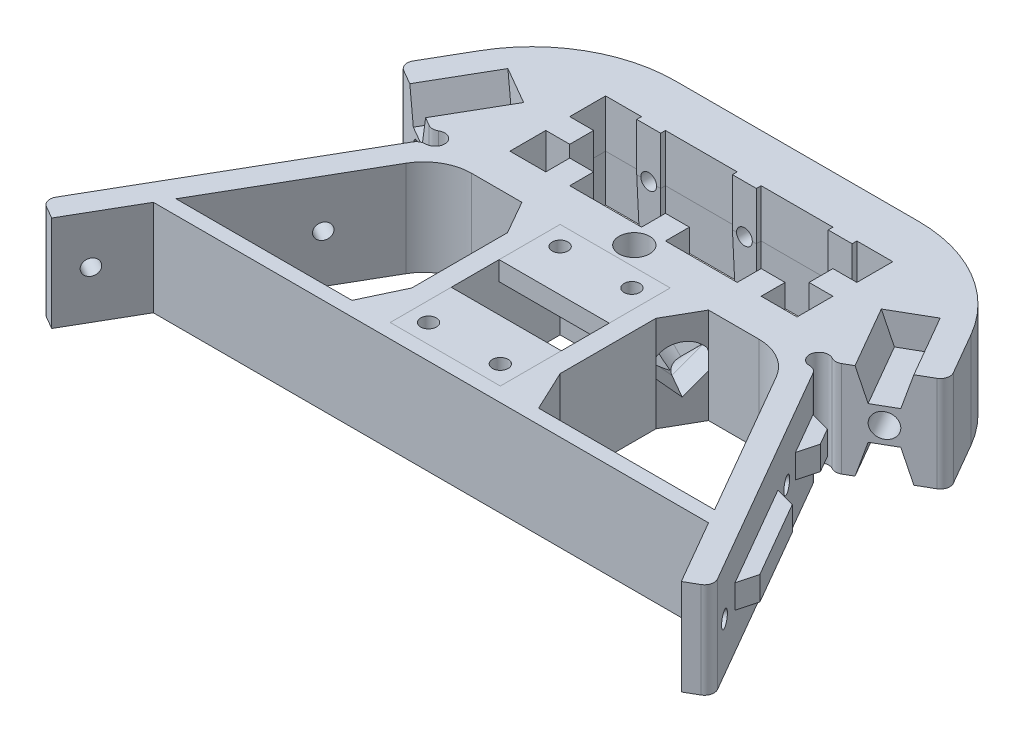
SolidWorks part; units mm, degrees
ref_plane "Front Plane" through (0, 0, 0) normal (0, 0, 1) x (1, 0, 0)
ref_plane "Top Plane" through (0, 0, 0) normal (0, 1, 0) x (1, 0, 0)
ref_plane "Right Plane" through (0, 0, 0) normal (1, 0, 0) x (0, 0, -1)
sketch "Sketch1" plane through (0, 0, 0) normal (0, 1, 0) x (1, 0, 0)
  line L0 (-30, -18) -> (30, -18)
  line L1 (-30, 10) -> (-22.5, 10)
  line L2 (-46.46, 5.4904) -> (-53.96, -7.5) construction
  line L3 (-30, -10) -> (-22.5, -10)
  line L4 (30, 10) -> (30, 2.5)
  line L5 (0, 0) -> (0, -75.5561) construction
  line L6 (38.6603, -23) -> (65.7735, -69.9615)
  line L7 (65.7735, -69.9615) -> (68.3716, -68.4615)
  line L8 (69.1036, -65.7295) -> (41.8357, -18.5)
  line L9 (43.1036, -13.7679) -> (55.6921, -6.5)
  line L10 (56.4241, -3.7679) -> (51.362, 5)
  line L11 (25.3812, 20) -> (-25.3812, 20)
  line L12 (43.5677, -13.5) -> (36.0677, -0.5096) construction
  line L13 (36.0677, -0.5096) -> (46.46, 5.4904) construction
  line L14 (46.46, 5.4904) -> (53.96, -7.5) construction
  line L15 (-36.0677, -0.5096) -> (-46.46, 5.4904) construction
  line L16 (-43.5677, -13.5) -> (-36.0677, -0.5096) construction
  line L17 (-56.4241, -3.7679) -> (-51.362, 5)
  line L18 (-43.1036, -13.7679) -> (-55.6921, -6.5)
  line L19 (-69.1036, -65.7295) -> (-41.8357, -18.5)
  line L20 (-65.7735, -69.9615) -> (-68.3716, -68.4615)
  line L21 (-38.6603, -23) -> (-65.7735, -69.9615)
  line L22 (-30, 10) -> (-30, 2.5)
  line L23 (30, 2.5) -> (25, 2.5)
  line L24 (25, 2.5) -> (25, -2.5)
  line L25 (25, -2.5) -> (30, -2.5)
  line L26 (30, -2.5) -> (30, -10)
  line L27 (22.5, -10) -> (22.5, -5)
  line L28 (22.5, -5) -> (17.5, -5)
  line L29 (17.5, -5) -> (17.5, -10)
  line L30 (22.5, -10) -> (30, -10)
  line L31 (17.5, 10) -> (17.5, 9)
  line L32 (17.5, 9) -> (22.5, 9)
  line L33 (22.5, 9) -> (22.5, 10)
  line L34 (22.5, 10) -> (30, 10)
  line L35 (2.5, -10) -> (2.5, -5)
  line L36 (2.5, -5) -> (-2.5, -5)
  line L37 (-2.5, -5) -> (-2.5, -10)
  line L38 (-2.5, 10) -> (-2.5, 9)
  line L39 (-2.5, 9) -> (2.5, 9)
  line L40 (2.5, 9) -> (2.5, 10)
  line L41 (-17.5, -10) -> (-17.5, -5)
  line L42 (-17.5, -5) -> (-22.5, -5)
  line L43 (-22.5, -5) -> (-22.5, -10)
  line L44 (-22.5, 10) -> (-22.5, 9)
  line L45 (-22.5, 9) -> (-17.5, 9)
  line L46 (-17.5, 9) -> (-17.5, 10)
  line L47 (-17.5, 10) -> (-2.5, 10)
  line L48 (-17.5, -10) -> (-2.5, -10)
  line L49 (2.5, -10) -> (17.5, -10)
  line L50 (2.5, 10) -> (17.5, 10)
  line L51 (-25, -2.5) -> (-30, -2.5)
  line L52 (-25, 2.5) -> (-25, -2.5)
  line L53 (-30, 2.5) -> (-25, 2.5)
  line L54 (-30, -2.5) -> (-30, -10)
  circle A0 centre (0, 0) radius 31.6228 construction
  arc A1 (30, -18) -> (38.6603, -23) centre (30, -28) cw
  arc A2 (51.362, 5) -> (25.3812, 20) centre (25.3812, -10) ccw
  arc A3 (41.1036, -13.7679) -> (40.1036, -17.5) centre (40.1036, -15.5) ccw
  arc A4 (68.3716, -68.4615) -> (69.1036, -65.7295) centre (67.3716, -66.7295) ccw
  arc A5 (55.6921, -6.5) -> (56.4241, -3.7679) centre (54.6921, -4.7679) ccw
  arc A6 (40.1036, -17.5) -> (41.8357, -18.5) centre (40.1036, -19.5) cw
  arc A7 (41.1036, -13.7679) -> (43.1036, -13.7679) centre (42.1036, -12.0359) ccw
  arc A8 (-41.1036, -13.7679) -> (-43.1036, -13.7679) centre (-42.1036, -12.0359) cw
  arc A9 (-40.1036, -17.5) -> (-41.8357, -18.5) centre (-40.1036, -19.5) ccw
  arc A10 (-55.6921, -6.5) -> (-56.4241, -3.7679) centre (-54.6921, -4.7679) cw
  arc A11 (-68.3716, -68.4615) -> (-69.1036, -65.7295) centre (-67.3716, -66.7295) cw
  arc A12 (-41.1036, -13.7679) -> (-40.1036, -17.5) centre (-40.1036, -15.5) cw
  arc A13 (-51.362, 5) -> (-25.3812, 20) centre (-25.3812, -10) cw
  arc A14 (-30, -18) -> (-38.6603, -23) centre (-30, -28) ccw
  point P7 (-57.4241, -5.5)
  point P9 (0, -18)
  point P22 (35.7735, -18)
  point P27 (0, 10)
  point P30 (70.1036, -67.4615)
  point P33 (57.4241, -5.5)
  point P61 (0, 20)
  point P65 (-70.1036, -67.4615)
  point P66 (-35.7735, -18)
  dimension "D12" = 10
  dimension "D14" = 30
  dimension "D16" = 2
  dimension "D17" = 2
  dimension "D2" = 30
  dimension "D3" = 5
  dimension "D4" = 8
  dimension "D5" = 60
  dimension "D6" = 20
  dimension "D7" = 30
  dimension "D8" = 10
  dimension "D9" = 4
  dimension "D10" = 12
  dimension "D11" = 15
  dimension "D13" = 20
  dimension "D18" = 5
  dimension "D19" = 2.5
  dimension "D20" = 5
  dimension "D21" = 5
  dimension "D22" = 5
  dimension "D23" = 7.5
  dimension "D24" = 1
  dimension "D26" = 20
  dimension "D25" = 3
extrude "Boss-Extrude1" add sketch "Sketch1" along normal blind 20
sketch "Sketch2" plane through (16.7376, 0, 28.9904) normal (0.5, 0, 0.866) x (0.866, 0, -0.5)
  line L0 (30.4449, 0) -> (44.9808, 0) construction
  line L1 (26.9808, 20) -> (26.9808, 0) construction
  circle A0 centre (36.9808, 10) radius 5
  dimension "D1" = 10
  dimension "D2" = 10
  dimension "D3" = 10
extrude "Cut-Extrude1" cut sketch "Sketch2" against normal through all
sketch "Sketch3" plane through (16.7376, 0, 28.9904) normal (0.5, 0, 0.866) x (0.866, 0, -0.5)
  circle A0 centre (36.9808, 10) radius 5
  circle A1 centre (36.9808, 10) radius 5 construction
  circle A2 centre (36.9808, 10) radius 2.5
  dimension "D1" = 5
extrude "Boss-Extrude2" add sketch "Sketch3" against normal blind 16
sketch "Sketch4" plane through (16.7376, 0, 28.9904) normal (0.5, 0, 0.866) x (0.866, 0, -0.5)
  line L0 (36.9808, 10) -> (44.9808, 10) construction
  line L1 (44.9808, 20) -> (44.9808, 0) construction
  line L2 (32.4808, 20) -> (34.4808, 13.5)
  line L3 (30.4449, 20) -> (44.9808, 20) construction
  line L4 (34.4808, 13.5) -> (39.4808, 13.5)
  line L5 (39.4808, 13.5) -> (41.4808, 20)
  line L6 (41.4808, 20) -> (32.4808, 20)
  line L7 (36.9808, 13.5) -> (36.9808, 20) construction
  line L8 (41.4808, 0) -> (32.4808, 0)
  line L9 (39.4808, 6.5) -> (41.4808, 0)
  line L10 (34.4808, 6.5) -> (39.4808, 6.5)
  line L11 (32.4808, 0) -> (34.4808, 6.5)
  dimension "D1" = 9
  dimension "D2" = 5
  dimension "D3" = 6.5
extrude "Cut-Extrude2" cut sketch "Sketch4" against normal blind 15
sketch "Sketch7" plane through (0, 0, -20) normal (0, 0, -1) x (-1, 0, 0)
  line L0 (-20, 10) -> (20, 10) construction
  circle A0 centre (-20, 10) radius 1.65
  circle A1 centre (0, 10) radius 1.65
  circle A2 centre (20, 10) radius 1.65
  dimension "D1" = 3.3
  dimension "D3" = 40
  dimension "D4" = 10
  dimension "D2" = 3
extrude "Cut-Extrude4" cut sketch "Sketch7" against normal up to next
sketch "Sketch8" plane through (0, 0, -20) normal (0, 0, -1) x (-1, 0, 0)
  circle A0 centre (-20, 10) radius 6
  circle A1 centre (-20, 10) radius 1.65 construction
  circle A2 centre (0, 10) radius 6
  circle A3 centre (20, 10) radius 6
  circle A4 centre (20, 10) radius 1.65 construction
  dimension "D1" = 12
  dimension "D2" = 3
extrude "Cut-Extrude5" cut sketch "Sketch8" against normal offset from surface (4 mm away) 7 up to face at (1.65, 10, -9)
sketch "Sketch9" plane through (0, 0, 0) normal (0, 1, 0) x (1, 0, 0)
  line L0 (-11.5, -40) -> (11.5, -40) construction
  line L1 (2.5, -10) -> (17.5, -10) construction
  line L2 (-11.5, -30) -> (11.5, -30) construction
  line L3 (-11.5, -30) -> (-11.5, -40)
  line L4 (11.5, -30) -> (11.5, -40)
  line L5 (0, -30) -> (0, 0) construction
  line L6 (-19.5, -18) -> (-15.5, -25)
  line L7 (-30, -18) -> (30, -18) construction
  line L8 (-15.5, -25) -> (-15.5, -45)
  line L9 (-15.5, -45) -> (-19.5, -53.5)
  line L10 (-56.2694, -53.5) -> (-19.5, -53.5)
  line L11 (19.5, -53.5) -> (15.5, -45)
  line L12 (15.5, -45) -> (15.5, -25)
  line L13 (15.5, -25) -> (19.5, -18)
  line L14 (-19.5, -18) -> (-11.5, -18)
  line L15 (-11.5, -35) -> (11.5, -35) construction
  line L16 (11.5, -30) -> (11.5, -18)
  line L17 (-11.5, -30) -> (-11.5, -18)
  line L18 (11.5, -18) -> (19.5, -18)
  line L19 (-11.5, -40) -> (-11.5, -53.5)
  line L20 (-11.5, -53.5) -> (11.5, -53.5)
  line L21 (11.5, -53.5) -> (11.5, -40)
  line L30 (-65.7735, -69.9615) -> (-38.6603, -23) construction
  line L31 (38.6603, -23) -> (65.7735, -69.9615) construction
  line L32 (19.5, -53.5) -> (56.2694, -53.5)
  line L33 (-58.0015, -56.5) -> (58.0015, -56.5)
  line L34 (58.0015, -56.5) -> (56.2694, -53.5)
  line L35 (-58.0015, -56.5) -> (-56.2694, -53.5)
  circle A0 centre (0, -20.5) radius 1.65 construction
  circle A1 centre (0, -49.5) radius 1.65 construction
  dimension "D6" = 3.3
  dimension "D11" = 2.5
  dimension "D1" = 30
  dimension "D2" = 10
  dimension "D3" = 23
  dimension "D4" = 4
  dimension "D5" = 4
  dimension "D7" = 7
  dimension "D8" = 8.5
  dimension "D9" = 7
  dimension "D10" = 20
  dimension "D14" = 4
  dimension "D15" = 4
  dimension "D16" = 4
  dimension "D17" = 3
extrude "Boss-Extrude3" add sketch "Sketch9" along normal up to surface (20 mm away) up to face at (6.0019, 20, 19.8008)
sketch "Sketch11" plane through (23.366, 0, -13.4904) normal (0.866, 0, -0.5) x (-0.5, 0, -0.866)
  line L1 (-81.4752, 12.5) -> (-56.9393, 12.5)
  line L2 (-81.4752, 12.5) -> (-81.4752, 7.5)
  line L3 (-81.4752, 7.5) -> (-56.9393, 7.5)
  line L4 (-36.9393, 12.5) -> (-36.9393, 7.5)
  line L5 (-36.9393, 20) -> (-36.9393, 0) construction
  line L6 (-91.4752, 0) -> (-36.9393, 0) construction
  line L7 (-46.9393, 12.5) -> (-46.9393, 7.5)
  line L8 (-56.9393, 12.5) -> (-56.9393, 7.5)
  line L9 (-46.9393, 12.5) -> (-36.9393, 12.5)
  line L10 (-46.9393, 7.5) -> (-36.9393, 7.5)
  line L11 (-91.4752, 20) -> (-91.4752, 0) construction
  dimension "D1" = 5
  dimension "D2" = 7.5
  dimension "D3" = 10
  dimension "D4" = 10
  dimension "D5" = 10
extrude "Boss-Extrude5" add sketch "Sketch11" along normal blind 3
chamfer "Chamfer1" distance 3 angle 45 4 edges at (44.4338, 10, 17) (49.4338, 10, 25.6603) (54.4338, 10, 34.3205) (66.7017, 10, 55.5692)
sketch "Sketch13" plane through (23.366, 0, -13.4904) normal (0.866, 0, -0.5) x (-0.5, 0, -0.866)
  line L0 (-56.9393, 10) -> (-46.9393, 10) construction
  line L1 (-56.9393, 7.5) -> (-56.9393, 12.5) construction
  line L2 (-46.9393, 12.5) -> (-46.9393, 7.5) construction
  line L3 (-81.4752, 10) -> (-93.4752, 10) construction
  line L4 (-81.4752, 12.5) -> (-81.4752, 7.5) construction
  line L5 (-93.4752, 20) -> (-93.4752, 0) construction
  circle A0 centre (-51.9393, 10) radius 1.65
  circle A1 centre (-87.4752, 10) radius 1.65
  dimension "D1" = 3.3
  dimension "D2" = 3.3
extrude "Cut-Extrude6" cut sketch "Sketch13" against normal up to next
mirror "Mirror2" about plane through (0, 0, 0) normal (1, 0, 0) of "Cut-Extrude6", "Chamfer1", "Boss-Extrude5", "Cut-Extrude2", "Boss-Extrude2", "Cut-Extrude1"
ref_plane "Plane2" through (0, 10, 0) normal (0, 1, 0) x (1, 0, 0)
sketch "Sketch15" plane through (0, 10, 0) normal (0, 1, 0) x (1, 0, 0)
  line L0 (-10, -10) -> (-10, -14.3127)
  line L1 (-17.5, -10) -> (-2.5, -10) construction
  line L2 (-12.5193, -18.6539) -> (-17.5, -21.5)
  line L3 (-19.5, -18) -> (-15.5, -25) construction
  arc A0 (-10, -14.3127) -> (-12.5193, -18.6539) centre (-15, -14.3127) cw
  dimension "D1" = 5
sketch "Sketch16" plane through (0, 0, 10) normal (0, 0, -1) x (-1, 0, 0)
  line L0 (5, 10) -> (10, 5)
  line L1 (10, 5) -> (15, 10)
  arc A0 (15, 10) -> (5, 10) centre (10, 10) ccw
  dimension "D1" = 10
sketch "Sketch17" plane through (0, 20, 0) normal (0, 1, 0) x (1, 0, 0)
  line L0 (-11.5, -53.5) -> (-11.5, -18) construction
  line L1 (11.5, -18) -> (-11.5, -18)
  line L2 (11.5, -18) -> (11.5, -30.75)
  line L3 (11.5, -30.75) -> (-11.5, -30.75)
  line L4 (-11.5, -18) -> (-11.5, -30.75)
  line L5 (-11.5, -18) -> (11.5, -18) construction
  line L6 (11.5, -18) -> (11.5, -53.5) construction
  line L7 (11.5, -53.5) -> (-11.5, -53.5) construction
  line L9 (-11.5, -53.5) -> (11.5, -53.5)
  line L10 (-11.5, -53.5) -> (-11.5, -40.75)
  line L11 (-11.5, -40.75) -> (11.5, -40.75)
  line L12 (11.5, -53.5) -> (11.5, -40.75)
  line L13 (22.5, -10) -> (30, -10) construction
  circle A0 centre (-7.5, -49.5) radius 1.65
  circle A1 centre (7.5, -49.5) radius 1.65
  circle A2 centre (7.5, -22) radius 1.65
  circle A3 centre (-7.5, -22) radius 1.65
  dimension "D3" = 3.3
  dimension "D4" = 4
  dimension "D5" = 4
  dimension "D8" = 4
  dimension "D1" = 10
  dimension "D2" = 30.75
  dimension "D9" = 4
  dimension "D6" = 2
  dimension "D7" = 2
extrude "Boss-Extrude6" add sketch "Sketch17" against normal blind 4 separate body
sweep "Cut-Sweep1" cut profiles "Sketch16" path "Sketch15"
mirror "Mirror3" about plane through (0, 0, 0) normal (1, 0, 0) of "Cut-Sweep1"
sketch "Sketch18" plane through (0, 20, 0) normal (0, 1, 0) x (1, 0, 0)
  line L0 (0, -18) -> (0, -10) construction
  line L1 (-11.5, -18) -> (11.5, -18) construction
  line L2 (2.5, -10) -> (17.5, -10) construction
  circle A0 centre (0, -14) radius 3.2
  dimension "D1" = 6.4
extrude "Cut-Extrude7" cut sketch "Sketch18" against normal blind 10
chamfer "Chamfer3" distance 10 distance2 0.25 36 edges at (26.25, 0, -10) (30, 0, -6.25) (27.5, 0, -2.5) (25, 0, 0) (27.5, 0, 2.5) (30, 0, 6.25) (26.25, 0, 10) (22.5, 0, 7.5) (20, 0, 5) (17.5, 0, 7.5) (10, 0, 10) (2.5, 0, 7.5) (0, 0, 5) (-2.5, 0, 7.5) (-10, 0, 10) (-17.5, 0, 7.5) (-20, 0, 5) (-22.5, 0, 7.5) (-26.25, 0, 10) (-30, 0, 6.25) (-27.5, 0, 2.5) (-25, 0, 0) (-27.5, 0, -2.5) (-30, 0, -6.25) (-26.25, 0, -10) (-22.5, 0, -9.5) (-20, 0, -9) (-17.5, 0, -9.5) (-10, 0, -10) (-2.5, 0, -9.5) (0, 0, -9) (2.5, 0, -9.5) (10, 0, -10) (17.5, 0, -9.5) (20, 0, -9) (22.5, 0, -9.5) first distance on face at (26.25, 10, -10) first distance on face at (30, 10, -6.25) first distance on face at (27.5, 10, -2.5) first distance on face at (25, 10, 0) first distance on face at (27.5, 10, 2.5) first distance on face at (30, 10, 6.25) first distance on face at (26.25, 10, 10) first distance on face at (22.5, 10, 7.5) first distance on face at (20, 10, 5) first distance on face at (17.5, 10, 7.5) first distance on face at (10, 10, 10) first distance on face at (2.5, 10, 7.5) first distance on face at (0, 10, 5) first distance on face at (-2.5, 10, 7.5) first distance on face at (-10, 10, 10) first distance on face at (-17.5, 10, 7.5) first distance on face at (-20, 10, 5) first distance on face at (-22.5, 10, 7.5) first distance on face at (-26.25, 10, 10) first distance on face at (-30, 10, 6.25) first distance on face at (-27.5, 10, 2.5) first distance on face at (-25, 10, 0) first distance on face at (-27.5, 10, -2.5) first distance on face at (-30, 10, -6.25) first distance on face at (-26.25, 10, -10) first distance on face at (-22.5, 10, -9.5) first distance on face at (-18.35, 10, -9) first distance on face at (-17.5, 10, -9.5) first distance on face at (-10, 10, -10) first distance on face at (-2.5, 10, -9.5) first distance on face at (1.65, 10, -9) first distance on face at (2.5, 10, -9.5) first distance on face at (10, 10, -10) first distance on face at (17.5, 10, -9.5) first distance on face at (21.65, 10, -9) first distance on face at (22.5, 10, -9.5)
